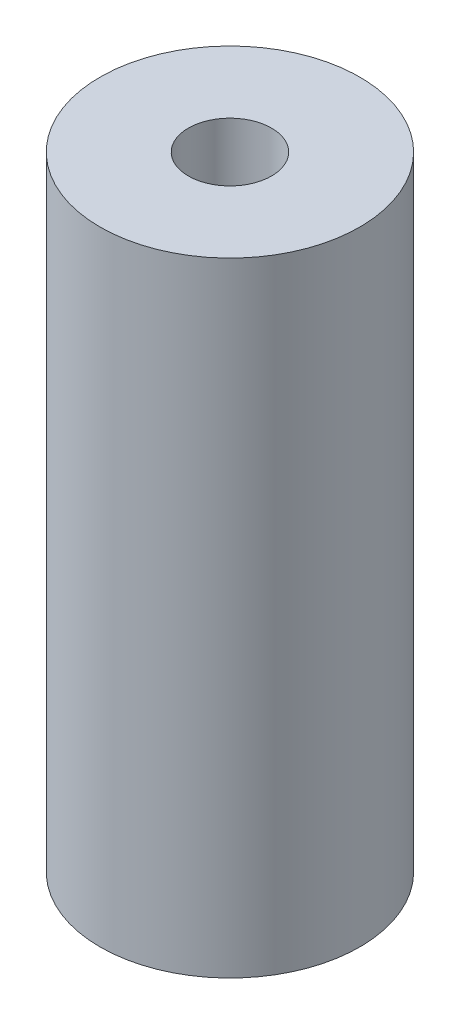
SolidWorks part; units mm, degrees
ref_plane "Front" through (0, 0, 0) normal (0, 0, 1) x (1, 0, 0)
ref_plane "Top" through (0, 0, 0) normal (0, 1, 0) x (1, 0, 0)
ref_plane "Right" through (0, 0, 0) normal (1, 0, 0) x (0, 0, -1)
ref_axis "X" through (-80.9, 0, 0) along (1, 0, 0)
ref_axis "Y" through (0, -50, 0) along (0, 1, 0)
ref_axis "Z" through (0, 0, -80.9) along (0, 0, 1)
sketch "Sketch1" plane through (0, 0, 0) normal (0, 1, 0) x (1, 0, 0)
  circle A0 centre (0, 0) radius 2.5
  dimension "D1" = 5
extrude "Boss-Extrude1" add sketch "Sketch1" along normal mid plane 12
hole_wizard "M2x0.4 Tapped Hole1" positions "3DSketch1" profile "Sketch2" tap size "M2x0.4" standard "ANSI Metric"
sketch3d "3DSketch1"
  line L0 (0, -6, 0) -> (0, 0, 0) construction
  line L1 (0, 0, 0) -> (0, 6, 0) construction
  point P0 (0, 6, 0)
  point P2 (0, -6, 0)
sketch "Sketch2" plane through (0, 6, 0) normal (1, 0, 0) x (0, 0, 1)
  line L0 (0, 0) -> (0, 5.6807)
  line L1 (0, 5.6807) -> (0.8, 5.2)
  line L2 (0.8, 5.2) -> (0.8, 0)
  line L5 (0.8, 0) -> (0, 0)
  line L10 (0, 5.6807) -> (-0.8, 5.2) construction
  line L11 (0, -6.35) -> (0, 107.95) construction
  dimension "Tap Drill Dia." = 1.6
  dimension "Tap Drill Depth" = 5.2
  dimension "Drill Angle" = 118
cosmetic thread "Hole Thread1"
cosmetic thread "Hole Thread2"
